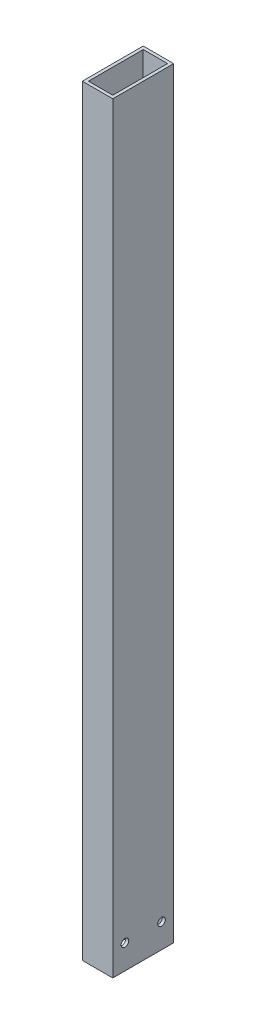
SolidWorks part; units mm, degrees
note: The reader was unsure of these and kept them because the rebuilt part matched: thickness of "Base-Flange1", "Sheet-Metal1", "Sheet-Metal2".
ref_plane "Front Plane" through (0, 0, 0) normal (0, 0, 1) x (1, 0, 0)
ref_plane "Top Plane" through (0, 0, 0) normal (0, 1, 0) x (1, 0, 0)
ref_plane "Right Plane" through (0, 0, 0) normal (1, 0, 0) x (0, 0, -1)
sketch "Sketch3" plane through (0, 0, 0) normal (0, 1, 0) x (1, 0, 0)
  line L1 (-10, -20) -> (10, -20)
  line L2 (-10, -20) -> (-10, 20)
  line L3 (-10, 20) -> (10, 20)
  line L4 (10, -20) -> (10, 20)
  line L5 (-10, -20) -> (10, 20) construction
  line L6 (-10, 20) -> (10, -20) construction
  line L7 (-8, -18) -> (8, -18)
  line L8 (-8, -18) -> (-8, 18)
  line L9 (-8, 18) -> (8, 18)
  line L10 (8, -18) -> (8, 18)
  line L11 (-8, -18) -> (8, 18) construction
  line L12 (-8, 18) -> (8, -18) construction
  point P0 (0, 0)
  point P6 (0, 0)
  dimension "D1" = 20
  dimension "D2" = 2
  dimension "D3" = 40
  dimension "D4" = 2
base flange "Base-Flange1" sketch "Sketch3" thickness 500 reverse thickness direction no parameters "D1"=0.7366
hole_wizard "Tap Drill for M6x1.0 Tap1" positions "Sketch5" profile "Sketch4" hole size "M6x1.0" standard "ANSI Metric" end condition through all
sketch "Sketch5" plane through (10, 0, 0) normal (1, 0, 0) x (0, 0, -1)
  point P0 (-12, -484)
  point P3 (12, -484)
sketch "Sketch4" plane through (10, -484, 12) normal (0, 1, 0) x (0, 0, -1)
  line L0 (0, 0) -> (0, 20)
  line L1 (0, 20) -> (2.5, 20)
  line L2 (2.5, 20) -> (2.5, 0)
  line L5 (2.5, 0) -> (0, 0)
  line L11 (0, -6.35) -> (0, 107.95) construction
  dimension "Thru Hole Dia." = 5
  dimension "Thru Hole Depth" = 20
sketch "Bend-Lines1" plane through (0, 0, 0) normal (0, 1, 0) x (1, 0, 0)
sketch "Bounding-Box1" plane through (0, 0, 0) normal (0, 1, 0) x (1, 0, 0)
sheet metal parameters "Sheet-Metal1" thickness 500 parameters "D1"=0.7366, "D7"=550
flat pattern "Flat-Pattern1" [suppressed]
sketch "Bend-Lines2" plane through (0, 0, 0) normal (0, 1, 0) x (1, 0, 0)
sketch "Bounding-Box2" [suppressed] plane through (0, 0, 0) normal (0, 1, 0) x (1, 0, 0)
sheet metal parameters "Sheet-Metal2" thickness 500 parameters "D1"=0.7366, "D7"=550
flat pattern "Flat-Pattern1"
sketch "Bend-Lines2" plane through (0, 0, 0) normal (0, 1, 0) x (1, 0, 0)
sketch "Bounding-Box2" [suppressed] plane through (0, 0, 0) normal (0, 1, 0) x (1, 0, 0)
